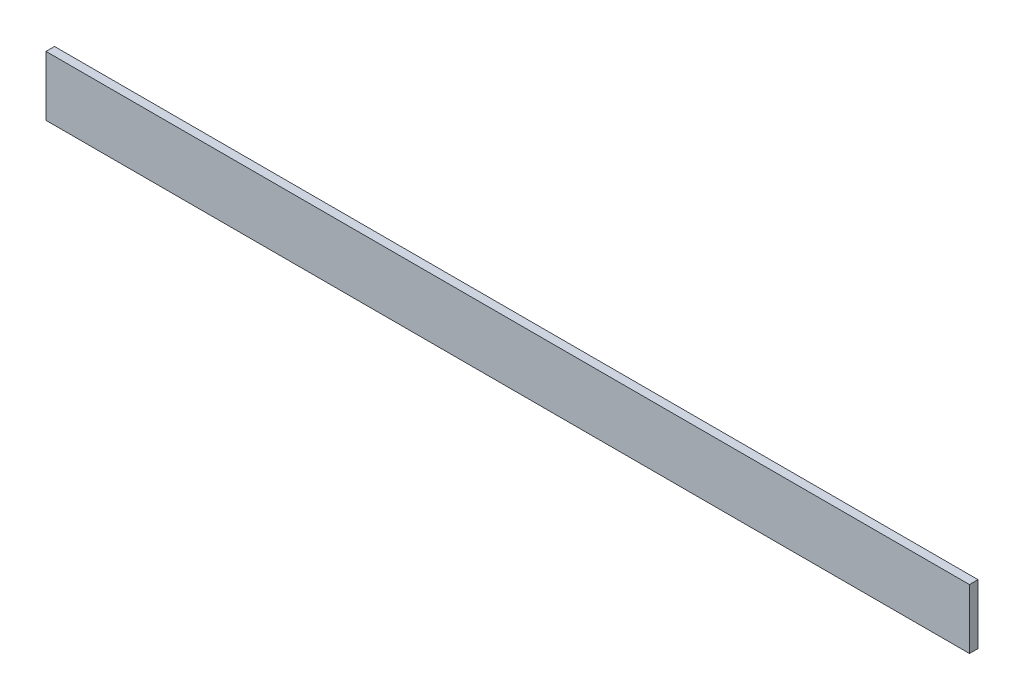
SolidWorks part; units mm, degrees
material "1.4016 (X6Cr17)"
ref_plane "前视基准面" through (0, 0, 0) normal (0, 0, 1) x (1, 0, 0)
ref_plane "上视基准面" through (0, 0, 0) normal (0, 1, 0) x (1, 0, 0)
ref_plane "右视基准面" through (0, 0, 0) normal (1, 0, 0) x (0, 0, -1)
sketch "草图2" plane through (0, 0, 0) normal (0, 0, 1) x (1, 0, 0)
  line L1 (-541, 35) -> (541, 35)
  line L2 (-541, 35) -> (-541, -35)
  line L3 (-541, -35) -> (541, -35)
  line L4 (541, 35) -> (541, -35)
  line L5 (-541, 35) -> (541, -35) construction
  line L6 (-541, -35) -> (541, 35) construction
  point P0 (0, 0)
  dimension "D1" = 1082
  dimension "D2" = 70
base flange "基体-法兰1" sketch "草图2" thickness 10 reverse thickness direction no parameters "D1"=2
ref_plane "基准面1" through (0, 0, -5) normal (0, 0, 1) x (1, 0, 0)
sketch "折弯-线1" plane through (0, 0, 0) normal (0, 1, 0) x (1, 0, 0)
sketch "边界框1" plane through (0, 0, 0) normal (0, 1, 0) x (1, 0, 0)
sheet metal parameters "钣金(1)" thickness 10 parameters "D1"=2
flat pattern "平板型式(1)" [suppressed]
sketch "折弯-线2" plane through (0, 0, 0) normal (0, 1, 0) x (1, 0, 0)
sketch "边界框2" [suppressed] plane through (0, 0, 0) normal (0, 1, 0) x (1, 0, 0)
